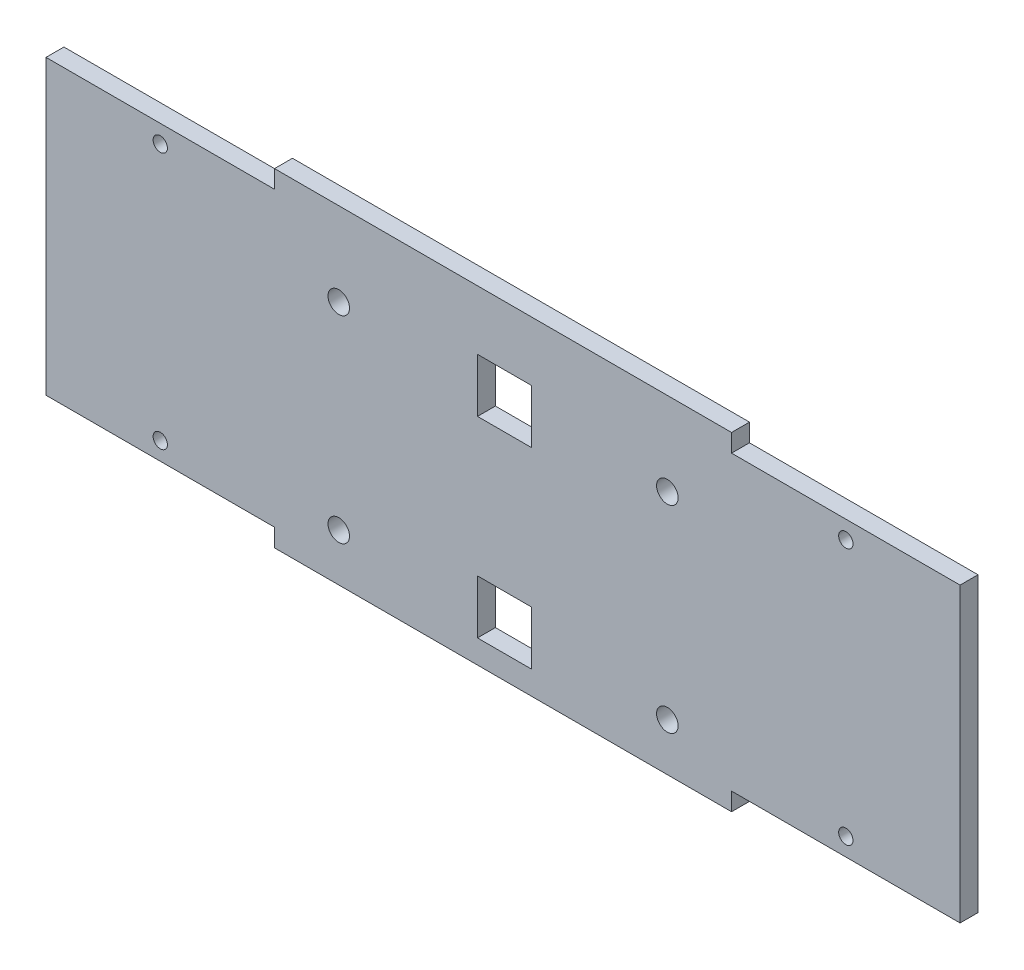
SolidWorks part; units mm, degrees
note: The reader was unsure of these and kept them because the rebuilt part matched: shared geometry of "Sketch8<3>".
ref_plane "Front Plane" through (0, 0, 0) normal (0, 0, 1) x (1, 0, 0)
ref_plane "Top Plane" through (0, 0, 0) normal (0, 1, 0) x (1, 0, 0)
ref_plane "Right Plane" through (0, 0, 0) normal (1, 0, 0) x (0, 0, -1)
sketch "Sketch1" plane through (0, 0, 0) normal (0, 0, 1) x (1, 0, 0)
  line L0 (191.25, 71.6376) -> (255, 71.6376)
  line L1 (0, 0) -> (63.75, 0)
  line L2 (0, 0) -> (0, 71.6376)
  line L3 (0, 71.6376) -> (63.75, 71.6376)
  line L4 (255, 0) -> (255, 71.6376)
  line L5 (0, 71.6376) -> (63.75, 71.6376)
  line L6 (0, 71.6376) -> (0, 66.6376)
  line L9 (191.25, 76.6376) -> (191.25, 71.6376)
  line L11 (63.75, 71.6376) -> (63.75, 76.6376)
  line L12 (63.75, 76.6376) -> (127.5, 76.6376)
  line L14 (127.5, 76.6376) -> (191.25, 76.6376)
  line L16 (191.25, 71.6376) -> (255, 71.6376)
  line L18 (191.25, 0) -> (255, 0)
  line L19 (191.25, 0) -> (255, 0)
  line L20 (127.5, -5) -> (191.25, -5)
  line L21 (63.75, -5) -> (127.5, -5)
  line L22 (63.75, 0) -> (63.75, -5)
  line L23 (191.25, -5) -> (191.25, 0)
  line L24 (0, 0) -> (63.75, 0)
  line L25 (0, 0) -> (63.75, 0)
  line L26 (191.25, 0) -> (255, 0)
  line L27 (0, 35.8188) -> (9.0697, 35.8188)
  line L28 (135.3704, 55.0794) -> (120.3704, 55.0794)
  line L29 (135.3704, 55.0794) -> (135.3704, 70.0794)
  line L30 (135.3704, 70.0794) -> (120.3704, 70.0794)
  line L31 (120.3704, 55.0794) -> (120.3704, 70.0794)
  line L32 (120.3704, 16.5582) -> (120.3704, 1.5582)
  line L33 (135.3704, 1.5582) -> (120.3704, 1.5582)
  line L34 (135.3704, 16.5582) -> (135.3704, 1.5582)
  line L35 (127.5, -5) -> (191.25, -5)
  line L36 (63.75, -5) -> (127.5, -5)
  line L37 (135.3704, 16.5582) -> (120.3704, 16.5582)
  circle A0 centre (81.6684, 63.3585) radius 3
  circle A1 centre (173.3316, 63.3585) radius 3
  circle A2 centre (81.6684, 8.2791) radius 3
  circle A3 centre (173.3316, 8.2791) radius 3
  point P28 (173.3316, 35.8188)
extrude "Boss-Extrude1" add sketch "Sketch1" along normal blind 5 contours L20 L23 L18 L4 L0 L9 L14 L12 L11 L3 L2 L1 L22 L21 A3 A2 A1 A0
sketch "Sketch2" plane through (0, 0, 0) normal (0, 0, -1) x (-1, 0, 0)
  line L0 (-31.875, 0) -> (-31.875, 5)
  line L1 (0, 0) -> (-63.75, 0) construction
  line L2 (-31.875, 71.6376) -> (-31.875, 66.6376)
  line L3 (0, 71.6376) -> (-63.75, 71.6376) construction
  line L4 (-127.5, -5) -> (-127.5, 28.2662)
  line L5 (-63.75, -5) -> (-191.25, -5) construction
  circle A0 centre (-31.875, 5) radius 1.5
  circle A1 centre (-31.875, 66.6376) radius 1.5
  circle A2 centre (-223.125, 66.6376) radius 1.5
  circle A3 centre (-223.125, 5) radius 1.5
extrude "Cut-Extrude1" cut sketch "Sketch2" against normal blind 185
sketch "Sketch3" plane through (0, 0, 0) normal (0, 0, -1) x (-1, 0, 0)
  circle A0 centre (-31.875, 5) radius 2
  circle A1 centre (-31.875, 66.6376) radius 2
  circle A2 centre (-223.125, 5) radius 2
  circle A3 centre (-223.125, 66.6376) radius 2
extrude "Cut-Extrude2" cut sketch "Sketch3" against normal blind 10
sketch "Sketch5" plane through (0, 71.6376, 0) normal (0, 1, 0) x (1, 0, 0)
  line L1 (255, 0) -> (191.25, 0)
  line L2 (255, 0) -> (255, -5)
  line L3 (255, -5) -> (191.25, -5)
  line L4 (191.25, 0) -> (191.25, -5)
sketch "Sketch6" plane through (0, 76.6376, 0) normal (0, 1, 0) x (1, 0, 0)
  line L1 (191.25, 0) -> (63.75, 0)
  line L2 (191.25, 0) -> (191.25, -5)
  line L3 (191.25, -5) -> (63.75, -5)
  line L4 (63.75, 0) -> (63.75, -5)
sketch "Sketch7" plane through (0, 71.6376, 0) normal (0, 1, 0) x (1, 0, 0)
  line L1 (63.75, 0) -> (0, 0)
  line L2 (63.75, 0) -> (63.75, -5)
  line L3 (63.75, -5) -> (0, -5)
  line L4 (0, 0) -> (0, -5)
extrude "Boss-Extrude3" add sketch "Sketch5" along normal blind 10
extrude "Boss-Extrude4" add sketch "Sketch6" along normal blind 10
extrude "Boss-Extrude5" add sketch "Sketch7" along normal blind 10
sketch "Sketch8" plane through (0, 0, 0) normal (0, 0, -1) x (-1, 0, 0)
  line L0 (-31.875, 66.6376) -> (-31.875, 76.6376)
  line L1 (-223.125, 66.6376) -> (-223.125, 76.6376)
  circle A0 centre (-31.875, 66.6376) radius 2
  circle A1 centre (-31.875, 76.6376) radius 2
  circle A2 centre (-223.125, 76.6376) radius 2
  circle A3 centre (-223.125, 66.6376) radius 2
extrude "Boss-Extrude6" add sketch "Sketch8" against normal up to surface (5 mm away) up to face at (127.5, 40.8188, 5)
extrude "Cut-Extrude3" cut sketch "Sketch8<3>" against normal blind 10
sketch "Sketch8<3>" plane through (0, 0, 0) normal (0, 0, -1) x (-1, 0, 0) same geometry as "Sketch8"
